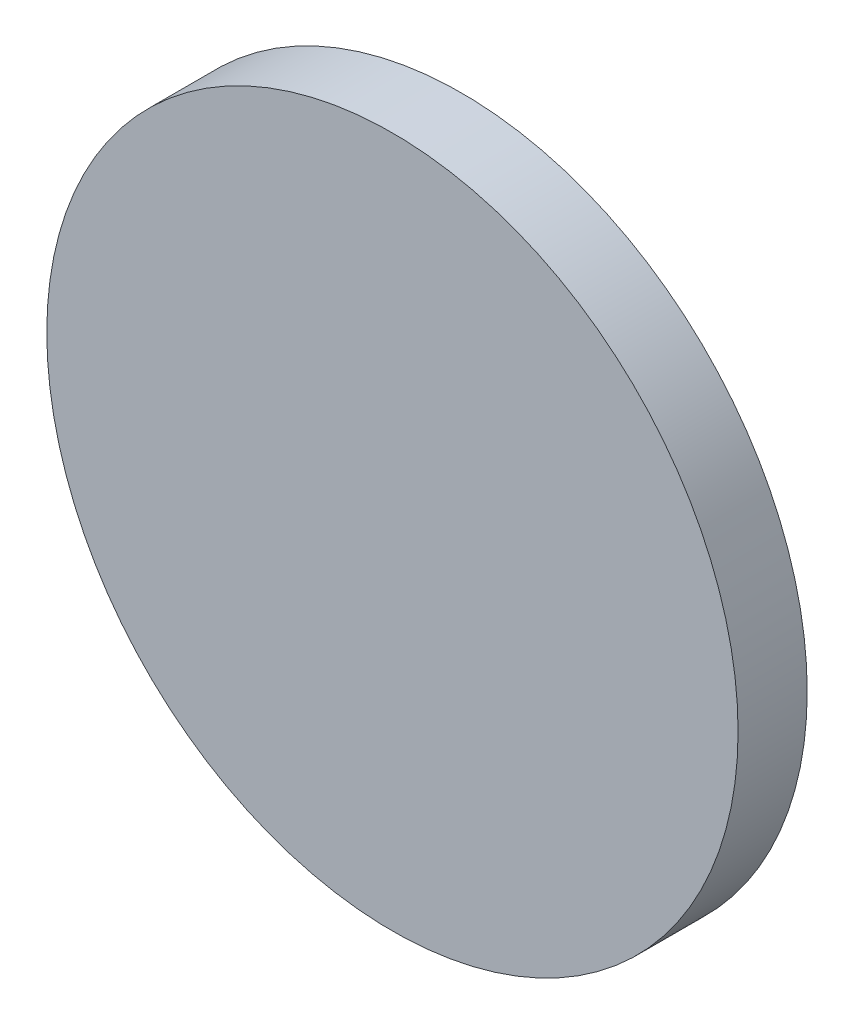
SolidWorks part; units mm, degrees
material "AISI 1020"
ref_plane "Ebene vorne" through (0, 0, 0) normal (0, 0, 1) x (1, 0, 0)
ref_plane "Ebene oben" through (0, 0, 0) normal (0, 1, 0) x (1, 0, 0)
ref_plane "Ebene rechts" through (0, 0, 0) normal (1, 0, 0) x (0, 0, -1)
sketch "Skizze2" plane through (0, 0, 0) normal (0, 0, 1) x (1, 0, 0)
  circle A0 centre (0, 0) radius 4.5
  dimension "D1" = 9
extrude "Aufsatz-Linear austragen1" add sketch "Skizze2" along normal blind 0.9
